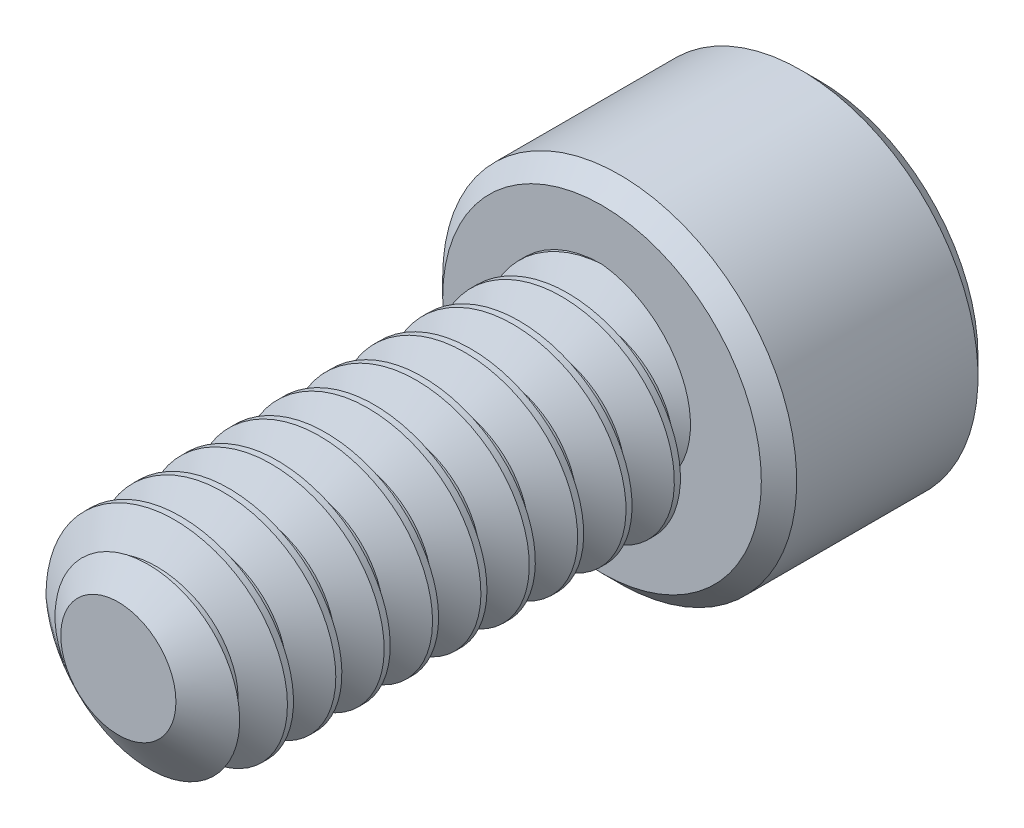
SolidWorks part; units mm, degrees
material "Alloy Steel"
ref_plane "Front Plane" through (0, 0, 0) normal (0, 0, 1) x (1, 0, 0)
ref_plane "Top Plane" through (0, 0, 0) normal (0, 1, 0) x (1, 0, 0)
ref_plane "Right Plane" through (0, 0, 0) normal (1, 0, 0) x (0, 0, -1)
sketch "Sketch1" plane through (0, 0, 0) normal (0, 0, 1) x (1, 0, 0)
  circle A0 centre (0, 0) radius 1.4224
  dimension "OD" = 2.8448
extrude "Extrude1" add sketch "Sketch1" against normal blind 6.35
sketch "Sketch2" plane through (0, 0, 0) normal (0, 0, 1) x (1, 0, 0)
  circle A0 centre (0, 0) radius 1.4224 construction
  circle A1 centre (0, 0) radius 1.4224
curve "Helix/Spiral1" pitch 0.635 height 6.985 radius 1.4224 centre (0, 0, 0) axis (0, 0, -1) start towards (0, 1, 0) parameters "pitch"=0.635
sketch "Sketch3" plane through (0, 0, 0) normal (1, 0, 0) x (0, 0, -1)
  line L0 (-0.5556, 1.4224) -> (-0.3175, 1.01)
  line L1 (-0.3175, 1.01) -> (-0.2381, 1.01)
  line L2 (-0.2381, 1.01) -> (0, 1.4224)
  line L3 (-0.5556, 1.4224) -> (0, 1.4224)
  line L4 (-0.2778, 1.4224) -> (-0.2778, 1.01) construction
  line L5 (-0.4366, 1.2162) -> (-0.1191, 1.2162) construction
  line L6 (0, 1.4224) -> (0, -1.4224) construction
  dimension "D1" = 0.0794
  dimension "D2" = 0.3175
  dimension "D3" = 60
sweep "Cut-Sweep1" cut profiles "Sketch3" path "Helix/Spiral1"
sketch "Sketch4" plane through (0, 0, 0) normal (1, 0, 0) x (0, 0, -1)
  line L0 (0.4666, 1.4224) -> (0, 0.756)
  line L1 (0, 0.756) -> (0, 1.4224)
  line L2 (0.4666, 1.4224) -> (0, 1.4224)
  line L3 (-0.5556, 1.4224) -> (0, 1.4224) construction
  line L4 (0, 0) -> (7.0209, 0) construction
  dimension "D1" = 55
  dimension "D2" = 0.254
revolve "Cut-Revolve1" cut sketch "Sketch4" angle 360 about L4
sketch "Sketch5" plane through (0, 0, 0) normal (1, 0, 0) x (0, 0, -1)
  line L0 (6.35, -1.0232) -> (6.35, 1.0149) construction
  line L1 (6.35, 1.5494) -> (38.1885, 1.5494)
  line L2 (6.35, 1.5494) -> (6.35, 0)
  line L3 (6.35, 0) -> (38.1, 0)
  line L4 (38.1, 1.2192) -> (38.1, 0)
  line L5 (38.1885, 1.5494) -> (38.1, 1.2192)
  line L6 (0, 0) -> (9.9695, 0) construction
  point P3 (38.1, 1.5494)
  point P10 (38.1, 1.5494)
  dimension "D1" = 0.3302
  dimension "Thread min" = 38.1
  dimension "D2" = 0.127
  dimension "D3" = 15
revolve "partially thread" [suppressed] add sketch "Sketch5" angle 360 about L6
sketch "Sketch6" plane through (0, 0, -6.35) normal (0, 0, -1) x (-1, 0, 0)
  circle A0 centre (0, 0) radius 2.3241
  dimension "head dia" = 4.6482
extrude "Extrude2" add sketch "Sketch6" along normal blind 2.8448
sketch "Sketch7" plane through (0, 0, -9.1948) normal (0, 0, -1) x (-1, 0, 0)
  line L1 (0, 1.3748) -> (-1.1906, 0.6874)
  line L2 (-1.1906, 0.6874) -> (-1.1906, -0.6874)
  line L3 (-1.1906, -0.6874) -> (0, -1.3748)
  line L4 (0, -1.3748) -> (1.1906, -0.6874)
  line L5 (1.1906, -0.6874) -> (1.1906, 0.6874)
  line L6 (1.1906, 0.6874) -> (0, 1.3748)
  circle A0 centre (0, 0) radius 1.1906 construction
  dimension "hex dia" = 2.3813
extrude "Cut-Extrude1" cut sketch "Sketch7" against normal blind 1.7859
sketch "Sketch8" plane through (0, 0, -9.1948) normal (0, 0, -1) x (-1, 0, 0)
  circle A0 centre (0, 0) radius 1.3748
extrude "Cut-Extrude2" cut sketch "Sketch8" against normal through all draft 45
chamfer "Chamfer1" distance 0.2324 angle 45 2 edges at (-2.3241, 0, -9.1948) (-2.3241, 0, -6.35)
sketch "Sketch9" plane through (0, 0, 0) normal (1, 0, 0) x (0, 0, -1)
  line L0 (0, 1.4224) -> (0, -1.4224) construction
  line L1 (6.6675, 1.4224) -> (6.6675, -1.4224) construction
  dimension "D1" = 6.6675
  dimension "D4" = 0.635
  dimension "D5" = 0.3302
equation "\"D3@Helix/Spiral1\" = \"screw length@Extrude1\"+\"pitch@Helix/Spiral1\""
equation "\"D1@Sketch3\" = \"pitch@Helix/Spiral1\"*.125"
equation "\"D2@Sketch3\" = \"pitch@Helix/Spiral1\"*.5"
equation "\"D1@Cut-Extrude1\" = \"hex dia@Sketch7\"*.75"
equation "\"D1@Chamfer1\" = \"head dia@Sketch6\"*.05"
equation "\"D1@Sketch9\" = \"pitch@Helix/Spiral1\"*10.5"
